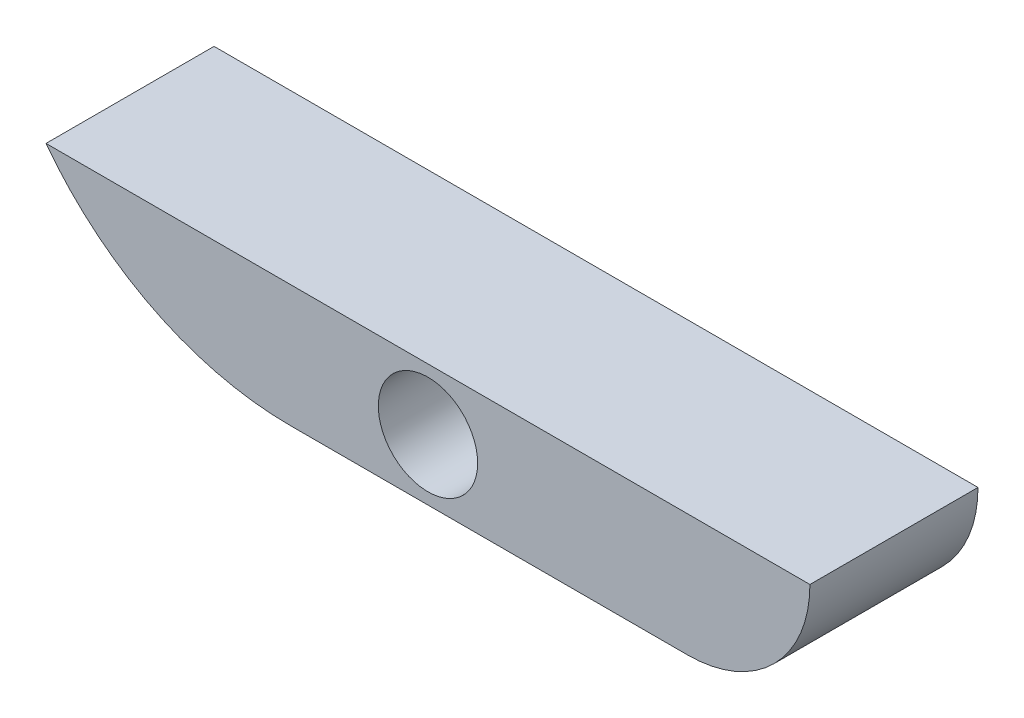
SolidWorks part; units mm, degrees
ref_plane "Front Plane" through (0, 0, 0) normal (0, 0, 1) x (1, 0, 0)
ref_plane "Top Plane" through (0, 0, 0) normal (0, 1, 0) x (1, 0, 0)
ref_plane "Right Plane" through (0, 0, 0) normal (1, 0, 0) x (0, 0, -1)
sketch "Sketch1" plane through (0, 0, 0) normal (0, 1, 0) x (1, 0, 0)
  line L1 (25, 5.5) -> (-25, 5.5)
  line L2 (25, 5.5) -> (25, -5.5)
  line L3 (25, -5.5) -> (-25, -5.5)
  line L4 (-25, 5.5) -> (-25, -5.5)
  line L5 (25, 5.5) -> (-25, -5.5) construction
  line L6 (25, -5.5) -> (-25, 5.5) construction
  point P0 (0, 0)
  dimension "D1" = 50
  dimension "D2" = 11
extrude "Boss-Extrude1" add sketch "Sketch1" along normal blind 8
fillet "Fillet1" radius 20 1 edges at (-25, 0, 0)
fillet "Fillet2" radius 8 1 edges at (25, 0, 0)
sketch "Sketch2" plane through (0, 0, 5.5) normal (0, 0, 1) x (1, 0, 0)
  line L0 (-25, 8) -> (25, 8) construction
  circle A0 centre (0, 4) radius 3.25
  dimension "D2" = 6.5
  dimension "D1" = 4
extrude "Cut-Extrude1" cut sketch "Sketch2" against normal blind 21
